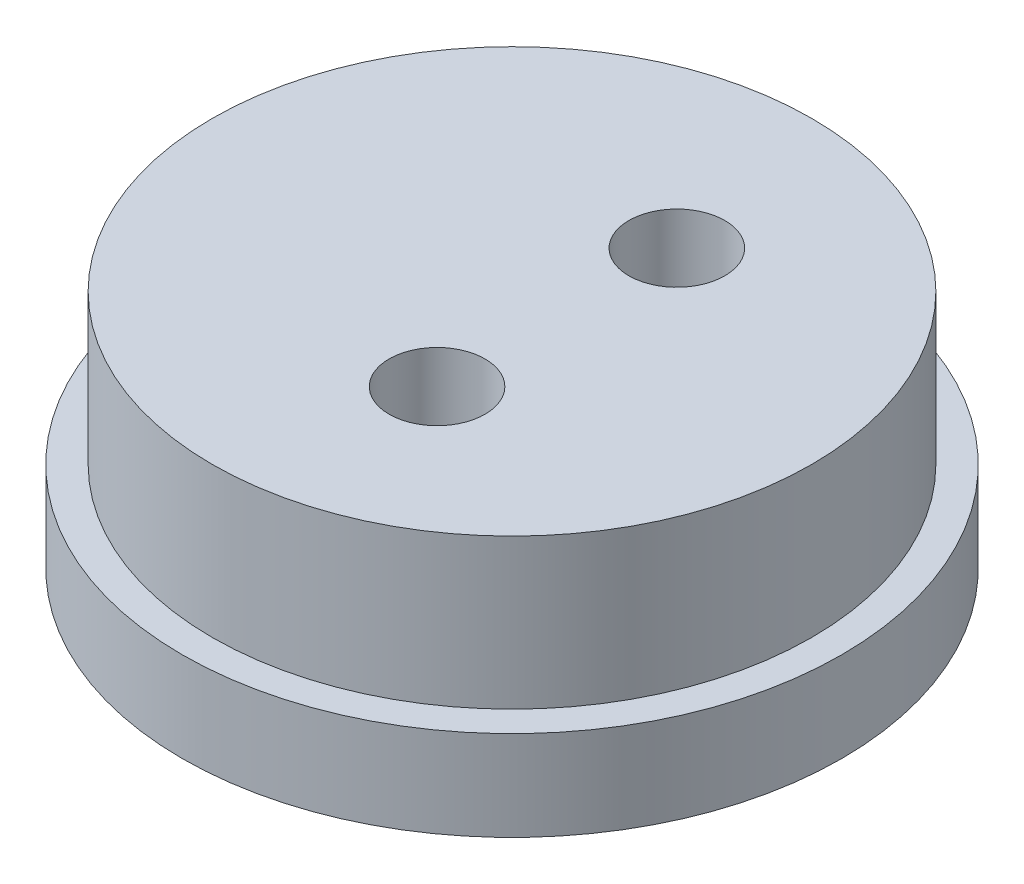
SolidWorks part; units mm, degrees
ref_plane "Front Plane" through (0, 0, 0) normal (0, 0, 1) x (1, 0, 0)
ref_plane "Top Plane" through (0, 0, 0) normal (0, 1, 0) x (1, 0, 0)
ref_plane "Right Plane" through (0, 0, 0) normal (1, 0, 0) x (0, 0, -1)
sketch "Sketch1" plane through (0, 0, 0) normal (0, 1, 0) x (1, 0, 0)
  line L0 (0, 0) -> (-1.5, 0) construction
  circle A1 centre (-1.5, 0) radius 10
  point P12 (0, 0)
  dimension "D3" = 20
  dimension "D2" = 1.5
extrude "Boss-Extrude1" add sketch "Sketch1" along normal blind 8
sketch "Sketch2" plane through (0, 0, 0) normal (0, -1, 0) x (1, 0, 0)
  line L0 (-12.8187, 0) -> (7.6603, 0) construction
  circle A0 centre (-1.5, 0) radius 11
  dimension "D2" = 22
  dimension "D1" = 1.5
extrude "Boss-Extrude2" add sketch "Sketch2" against normal blind 3
sketch "Sketch4" plane through (0, 8, 0) normal (0, 1, 0) x (1, 0, 0)
  line L0 (0, 8.8969) -> (0, -8.7328) construction
  circle A0 centre (0, 0) radius 4 construction
  circle A1 centre (0, 4) radius 1.6
  circle A2 centre (0, -4) radius 1.6
  dimension "D1" = 8
  dimension "D2" = 3.2
extrude "Cut-Extrude1" cut sketch "Sketch4" against normal through all
